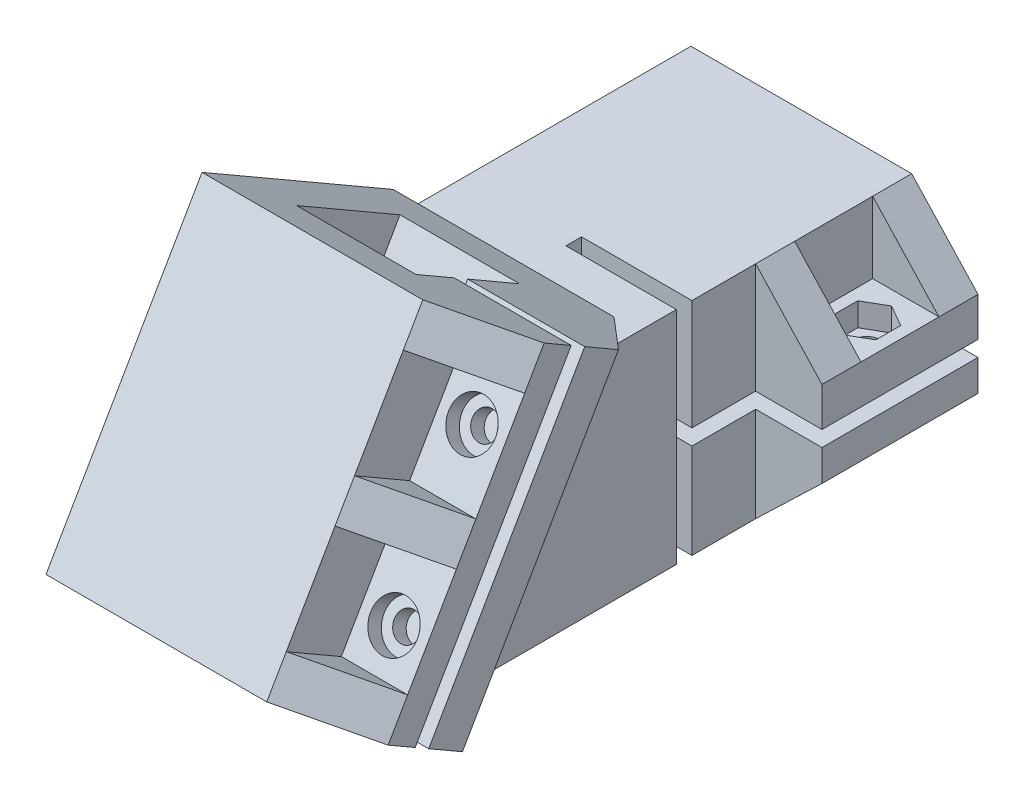
SolidWorks part; units mm, degrees
ref_plane "Plan de face" through (0, 0, 0) normal (0, 0, 1) x (1, 0, 0)
ref_plane "Plan de dessus" through (0, 0, 0) normal (0, 1, 0) x (1, 0, 0)
ref_plane "Plan de droite" through (0, 0, 0) normal (1, 0, 0) x (0, 0, -1)
sketch "Esquisse1" plane through (0, 0, 0) normal (0, 0, 1) x (1, 0, 0)
  line L0 (-14.15, 14.15) -> (-14.15, -14.15)
  line L1 (-10.15, 10.15) -> (10.15, 10.15)
  line L2 (-10.15, 10.15) -> (-10.15, -10.15)
  line L3 (-10.15, -10.15) -> (10.15, -10.15)
  line L4 (10.15, 10.15) -> (10.15, -10.15)
  line L5 (-10.15, 10.15) -> (10.15, -10.15) construction
  line L6 (-10.15, -10.15) -> (10.15, 10.15) construction
  line L7 (-14.15, -14.15) -> (14.15, -14.15)
  line L8 (14.15, 14.15) -> (14.15, -14.15)
  line L9 (-14.15, 14.15) -> (14.15, 14.15)
  line L10 (10.15, 0) -> (14.15, 0)
  line L11 (14.15, 0) -> (14.15, -2)
  line L12 (14.15, -2) -> (10.15, -2)
  line L13 (10.15, -2) -> (10.15, 0)
  line L14 (14.15, 0) -> (14.15, -2)
  line L15 (10.15, 0) -> (10.15, -2)
  point P0 (0, 0)
  dimension "D1" = 20.3
  dimension "D2" = 4
  dimension "D3" = 2
extrude "Boss.-Extru.1" add sketch "Esquisse1" along normal blind 20 contours L8 L12 L4 L3 L2 L1 L10 L9 L0 L7 | L13 L10 L11 L12 region at (0, 13.7498, 0)
extrude "Boss.-Extru.7" add sketch "Esquisse1<3>" against normal blind 20 contours L8 L12 L4 L3 L2 L1 L10 L9 L0 L7 region at (0, 13.7498, 0)
sketch "Esquisse1<3>" plane through (0, 0, 0) normal (0, 0, 1) x (1, 0, 0) same geometry as "Esquisse1"
ref_plane "Plan1" through (0, 2, 0) normal (0, -1, 0) x (-1, 0, 0)
sketch "Esquisse2" plane through (0, 2, 0) normal (0, -1, 0) x (-1, 0, 0)
  line L0 (-22.65, 0) -> (-14.15, 0) construction
  line L1 (-14.15, 20) -> (-22.65, 20)
  line L2 (-14.15, 20) -> (-14.15, -20)
  line L3 (-14.15, -20) -> (-22.65, -20) construction
  line L4 (-22.65, 20) -> (-22.65, -20)
  line L5 (-15.65, 8.4123) -> (-15.65, 11.5877)
  line L6 (-15.65, 11.5877) -> (-18.4, 13.1754)
  line L7 (-18.4, 13.1754) -> (-21.15, 11.5877)
  line L8 (-21.15, 11.5877) -> (-21.15, 8.4123)
  line L9 (-21.15, 8.4123) -> (-18.4, 6.8246)
  line L10 (-18.4, 6.8246) -> (-15.65, 8.4123)
  line L11 (-18.4, -6.8246) -> (-15.65, -8.4123) construction
  line L12 (-21.15, -8.4123) -> (-18.4, -6.8246) construction
  line L13 (-21.15, -11.5877) -> (-21.15, -8.4123) construction
  line L14 (-18.4, -13.1754) -> (-21.15, -11.5877) construction
  line L15 (-15.65, -11.5877) -> (-18.4, -13.1754) construction
  line L16 (-15.65, -8.4123) -> (-15.65, -11.5877) construction
  line L17 (-22.65, 0) -> (-14.15, -20) construction
  line L18 (-22.65, 0) -> (-14.15, 0)
  circle A0 centre (-18.4, 10) radius 2.75 construction
  circle A1 centre (-18.4, 10) radius 1.7
  circle A2 centre (-18.4, -10) radius 1.7 construction
  point P23 (-18.4, -10)
  dimension "D1" = 3.4
  dimension "D2" = 5.5
  dimension "D3" = 1.5
extrude "Boss.-Extru.2" add sketch "Esquisse2" along normal up to vertex (2 mm away) contours L1 L4 L3 L2 L10 L9 L8 L7 L6 L5 L11 L16 L15 L14 L13 L12 | L9 L10 L5 L6 L7 L8 A1 | L16 L11 L12 L13 L14 L15 A2 region at (14.3673, 2, -10) region at (17.067, 2, -7.6912) up to point (14.15, 0, -20)
extrude "Boss.-Extru.3" add sketch "Esquisse2<3>" against normal blind 3 contours L1 L4 L3 L2 L10 L9 L8 L7 L6 L5 L11 L16 L15 L14 L13 L12 region at (14.3673, 2, -10)
sketch "Esquisse2<3>" plane through (0, 2, 0) normal (0, -1, 0) x (-1, 0, 0) same geometry as "Esquisse2"
sketch "Esquisse3" plane through (0, -2, 0) normal (0, 1, 0) x (1, 0, 0)
  line L4 (22.65, 20) -> (14.15, 20)
  line L5 (14.15, 20) -> (14.15, 0)
  line L6 (14.15, 0) -> (22.65, 0)
  line L7 (22.65, 0) -> (22.65, 20)
  line L8 (22.65, 20) -> (14.15, 20)
  line L9 (14.15, 20) -> (14.15, 0)
  line L11 (22.65, 0) -> (22.65, 20)
  line L12 (14.15, 0) -> (22.65, 0)
  circle A0 centre (18.4, 10) radius 1.7 construction
  circle A1 centre (18.4, 10) radius 1.7
  dimension "D1" = 0
extrude "Boss.-Extru.4" add sketch "Esquisse3" against normal blind 2
sketch "Esquisse5" plane through (0, -4, 0) normal (0, -1, 0) x (1, 0, 0)
  line L0 (22.65, 0) -> (22.65, -20)
  line L3 (14.15, 0) -> (22.65, 0)
  line L5 (22.65, -20) -> (14.15, -20)
  line L6 (22.65, -20) -> (14.15, -20) construction
  line L7 (14.15, -20) -> (14.15, 0)
  line L8 (14.15, -20) -> (14.15, 0) construction
  circle A1 centre (18.4, -10) radius 3
  dimension "D1" = 6
extrude "Boss.-Extru.5" add sketch "Esquisse5" along normal blind 2
ref_plane "Plan3" through (0, 0, 0) normal (0, -1, 0) x (-1, 0, 0)
ref_plane "Plan6" through (0, 1.9522, -1.1271) normal (0, -0.866, 0.5) x (1, 0, 0)
ref_plane "Plan7" through (0, -8.6603, 5) normal (0, -0.866, 0.5) x (-1, 0, 0)
ref_plane "Plan8" through (0, -12.185, 7.035) normal (0, -0.866, 0.5) x (-1, 0, 0)
sketch "Esquisse6" plane through (0, -11.883, 7.5581) normal (0, -0.866, 0.5) x (-1, 0, 0)
  line L0 (-14.15, -23.7915) -> (14.15, -52.0915) construction
  line L1 (14.15, -23.7915) -> (-14.15, -23.7915)
  line L2 (14.15, -23.7915) -> (14.15, -52.0915)
  line L3 (14.15, -52.0915) -> (-14.15, -52.0915)
  line L4 (-14.15, -23.7915) -> (-14.15, -52.0915)
  line L6 (-7.65, -30.2915) -> (7.65, -30.2915)
  line L7 (-7.65, -30.2915) -> (-7.65, -45.5915)
  line L8 (-7.65, -45.5915) -> (7.65, -45.5915)
  line L9 (7.65, -30.2915) -> (7.65, -45.5915)
  line L10 (-7.65, -30.2915) -> (7.65, -45.5915) construction
  line L11 (-7.65, -45.5915) -> (7.65, -30.2915) construction
  point P5 (0, -37.9415)
  dimension "D1" = 15.3
extrude "Boss.-Extru.6" add sketch "Esquisse6" along normal blind 20 and the other way blind 20
sketch "Esquisse20" plane through (0, 0, 20) normal (0, 0, 1) x (1, 0, 0)
  line L4 (14.15, -14.15) -> (14.15, 14.15)
  line L5 (14.15, 14.15) -> (-14.15, 14.15)
  line L6 (-14.15, 14.15) -> (-14.15, -14.15)
  line L7 (-14.15, -14.15) -> (14.15, -14.15)
  line L8 (14.15, -14.15) -> (14.15, 14.15)
  line L9 (14.15, 14.15) -> (-14.15, 14.15)
  line L10 (-14.15, 14.15) -> (-14.15, -14.15)
  line L11 (-14.15, -14.15) -> (14.15, -14.15)
  dimension "D1" = 0
extrude "Boss.-Extru.12" add sketch "Esquisse20" along normal up to next
sketch "Esquisse7" plane through (0, -29.5055, 17.035) normal (0, -0.866, 0.5) x (1, 0, 0)
  line L0 (7.65, 38.5455) -> (14.15, 38.5455) construction
  line L1 (7.65, 30.8955) -> (7.65, 46.1955) construction
  line L2 (14.15, 24.3955) -> (14.15, 52.6955) construction
  line L3 (7.65, 38.5455) -> (14.15, 38.5455)
  line L4 (14.15, 38.5455) -> (14.15, 40.5455)
  line L5 (14.15, 40.5455) -> (7.65, 40.5455)
  line L6 (7.65, 40.5455) -> (7.65, 38.5455)
  dimension "D1" = 2
extrude "Enlèv. mat.-Extru.1" cut sketch "Esquisse7" against normal up to next
sketch "Esquisse8" plane through (0, -14.15, 0) normal (0, -1, 0) x (1, 0, 0)
  line L0 (14.15, 36.339) -> (14.15, -20) construction
  line L1 (14.15, 8.1695) -> (0, 8.1695)
  line L2 (14.15, 8.1695) -> (14.15, 10.1695)
  line L3 (14.15, 10.1695) -> (0, 10.1695)
  line L4 (0, 8.1695) -> (0, 10.1695)
  dimension "D1" = 2
extrude "Enlèv. mat.-Extru.2" cut sketch "Esquisse8" against normal up to next
sketch "Esquisse9" plane through (0, 19.2728, 33.3814) normal (0, 0.5, 0.866) x (1, 0, 0)
  line L0 (14.15, 5.93) -> (14.15, -34.07) construction
  line L1 (14.15, 5.93) -> (22.65, 5.93)
  line L2 (14.15, 5.93) -> (14.15, -34.07)
  line L3 (14.15, -34.07) -> (22.65, -34.07)
  line L4 (22.65, 5.93) -> (22.65, -34.07)
  line L5 (7.65, 5.93) -> (14.15, 5.93) construction
  line L6 (18.4, 5.93) -> (18.4, -34.07) construction
  line L7 (21.15, -5.6577) -> (21.15, -2.4823)
  line L8 (21.15, -2.4823) -> (18.4, -0.8946)
  line L9 (18.4, -0.8946) -> (15.65, -2.4823)
  line L10 (15.65, -2.4823) -> (15.65, -5.6577)
  line L11 (15.65, -5.6577) -> (18.4, -7.2454)
  line L12 (18.4, -7.2454) -> (21.15, -5.6577)
  line L13 (22.65, -14.07) -> (14.15, -14.07) construction
  line L14 (22.65, 5.93) -> (14.15, -14.07) construction
  line L15 (18.4, -20.8946) -> (21.15, -22.4823)
  line L16 (15.65, -22.4823) -> (18.4, -20.8946)
  line L17 (15.65, -25.6577) -> (15.65, -22.4823)
  line L18 (18.4, -27.2454) -> (15.65, -25.6577)
  line L19 (21.15, -25.6577) -> (18.4, -27.2454)
  line L20 (21.15, -22.4823) -> (21.15, -25.6577)
  circle A0 centre (18.4, -4.07) radius 2.75 construction
  circle A1 centre (18.4, -4.07) radius 1.7
  circle A2 centre (18.4, -24.07) radius 1.7
  line M16 (14.15, -34.07) -> (14.15, 5.93)
  dimension "D2" = 3.4
  dimension "D1" = 5.5
  dimension "D3" = 1.5
extrude "Boss.-Extru.8" add sketch "Esquisse9" against normal blind 5 contours L4 L1 L3 L12 L11 L10 L9 L8 L7 L15 L20 L19 L18 L17 L16 M16 region at (18.4, 7.0878, 40.4164)
extrude "Boss.-Extru.9" add sketch "Esquisse9<4>" against normal blind 2 contours L11 L12 L7 L8 L9 L10 A1 | L20 L15 L16 L17 L18 L19 A2 region at (19.733, 13.7485, 36.5708) region at (19.733, 0.427, 44.262)
sketch "Esquisse9<4>" plane through (0, 19.2728, 33.3814) normal (0, 0.5, 0.866) x (1, 0, 0) same geometry as "Esquisse9"
sketch "Esquisse10" plane through (0, 20.2728, 35.1134) normal (0, -0.5, -0.866) x (-1, 0, 0)
  line L4 (-22.65, 5.93) -> (-22.65, -34.07)
  line L5 (-22.65, -34.07) -> (-14.15, -34.07)
  line L6 (-14.15, -34.07) -> (-14.15, 5.93)
  line L7 (-14.15, 5.93) -> (-22.65, 5.93)
  line L8 (-22.65, 5.93) -> (-22.65, -34.07)
  line L9 (-22.65, -34.07) -> (-14.15, -34.07)
  line L10 (-14.15, -34.07) -> (-14.15, 5.93)
  line L11 (-14.15, 5.93) -> (-22.65, 5.93)
  circle A0 centre (-18.4, -24.07) radius 1.7 construction
  circle A1 centre (-18.4, -4.07) radius 1.7 construction
  circle A2 centre (-18.4, -24.07) radius 1.7
  circle A3 centre (-18.4, -4.07) radius 1.7
  dimension "D1" = 0
extrude "Boss.-Extru.10" add sketch "Esquisse10" against normal blind 2
sketch "Esquisse11" plane through (0, 21.2728, 36.8455) normal (0, 0.5, 0.866) x (1, 0, 0)
  line L4 (22.65, 5.93) -> (14.15, 5.93)
  line L5 (14.15, 5.93) -> (14.15, -34.07)
  line L6 (14.15, -34.07) -> (22.65, -34.07)
  line L7 (22.65, -34.07) -> (22.65, 5.93)
  line L8 (22.65, 5.93) -> (14.15, 5.93)
  line L9 (14.15, 5.93) -> (14.15, -34.07)
  line L10 (14.15, -34.07) -> (22.65, -34.07)
  line L11 (22.65, -34.07) -> (22.65, 5.93)
  circle A0 centre (18.4, -4.07) radius 3
  circle A1 centre (18.4, -24.07) radius 3
  dimension "D1" = 6
  dimension "D2" = 0
extrude "Boss.-Extru.11" add sketch "Esquisse11" along normal blind 2
sketch "Esquisse14" plane through (0, -29.5055, 17.035) normal (0, -0.866, 0.5) x (1, 0, 0)
  line L0 (14.15, 52.6955) -> (22.65, 44.5455)
rib "Nervure4" sketch "Esquisse14" sketch "Esquisse14" thickness 5 extrusion direction parallel to sketch draft on no parameters "D1"=5
ref_plane "Plan4" through (0, -12.185, 7.035) normal (0, -0.866, 0.5) x (-1, 0, 0)
sketch "Esquisse16" plane through (0, -29.5055, 17.035) normal (0, -0.866, 0.5) x (1, 0, 0)
  line L0 (22.65, 33.5455) -> (14.15, 24.3955)
rib "Nervure10" sketch "Esquisse16" sketch "Esquisse16" thickness 5 extrusion direction parallel to sketch draft on no parameters "D1"=5
pattern_linear "Répétition linéaire1" count 3 spacing 17.5 along (0, 0.866, -0.5) of "Nervure10", "Nervure4"
sketch "Esquisse17" plane through (0, 0, -20) normal (0, 0, -1) x (-1, 0, 0)
  line L0 (-22.65, 5) -> (-14.15, 14.15)
rib "Nervure11" sketch "Esquisse17" sketch "Esquisse17" thickness 5 extrusion direction parallel to sketch draft on no parameters "D1"=5
ref_plane "Plan5" through (0, 0, 0) normal (0, 1, 0) x (1, 0, 0)
sketch "Esquisse19" plane through (0, 0, 0) normal (0, 0, 1) x (1, 0, 0)
  line L0 (22.65, -6) -> (14.15, -14.15)
rib "Nervure17" sketch "Esquisse19" sketch "Esquisse19" thickness 5 extrusion direction parallel to sketch draft on no parameters "D1"=5
pattern_linear "Répétition linéaire2" count 2 spacing 15 along (0, 0, -1) of "Nervure17"
pattern_linear "Répétition linéaire3" count 2 spacing 15 along (0, 0, 1) of "Nervure11"
sketch "Esquisse21" plane through (0, 0, 0) normal (0, 0, -1) x (-1, 0, 0)
  line L0 (-14.15, -2.1523) -> (-14.15, 2.1778) construction
  line L1 (-10.15, -2) -> (-14.15, -2)
  line L2 (-10.15, -2) -> (-10.15, 0.0128)
  line L3 (-10.15, 0.0128) -> (-14.15, 0.0128)
  line L4 (-14.15, -2) -> (-14.15, 0.0128)
extrude "Enlèv. mat.-Extru.3" cut sketch "Esquisse21" against normal up to next
